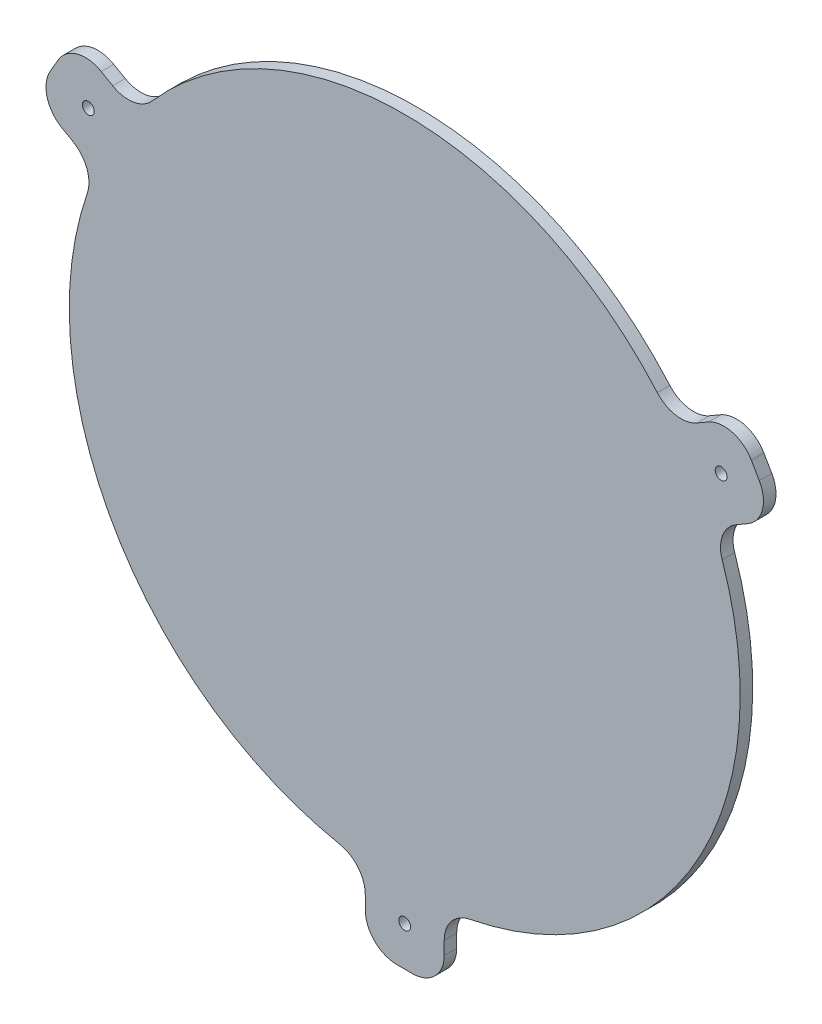
SolidWorks part; units mm, degrees
ref_plane "Front" through (0, 0, 0) normal (0, 0, 1) x (1, 0, 0)
ref_plane "Top" through (0, 0, 0) normal (0, 1, 0) x (1, 0, 0)
ref_plane "Right" through (0, 0, 0) normal (1, 0, 0) x (0, 0, -1)
sketch "Sketch1" plane through (0, 0, 0) normal (0, 0, 1) x (1, 0, 0)
  circle A0 centre (0, 0) radius 85
  dimension "D1" = 170
extrude "Boss-Extrude1" add sketch "Sketch1" along normal blind 3.175
sketch "Sketch2" plane through (0, 0, 0) normal (0, 0, 1) x (1, 0, 0)
  line L0 (0, 0) -> (0, -102.57) construction
  line L1 (-10, -84.4097) -> (10, -84.4097)
  line L2 (-10, -84.4097) -> (-10, -102.57)
  line L3 (-10, -102.57) -> (10, -102.57)
  line L4 (10, -84.4097) -> (10, -102.57)
  circle A0 centre (0, 0) radius 85 construction
  circle A1 centre (0, -92.57) radius 1.5
  dimension "D2" = 3
  dimension "D1" = 92.57
  dimension "D3" = 10
  dimension "D4" = 20
extrude "Boss-Extrude2" add sketch "Sketch2" along normal through all
fillet "Fillet1" radius 8 4 edges at (-10, -84.4097, 1.5875) (10, -84.4097, 1.5875) (-10, -102.57, 1.5875) (10, -102.57, 1.5875)
ref_axis "Axis1" through (0, 0, -80.9) along (0, 0, 1)
pattern_circular "CirPattern1" count 3 over 360 about axis through (0, 0, -80.9) along (0, 0, 1) of "Boss-Extrude2", "Fillet1"
